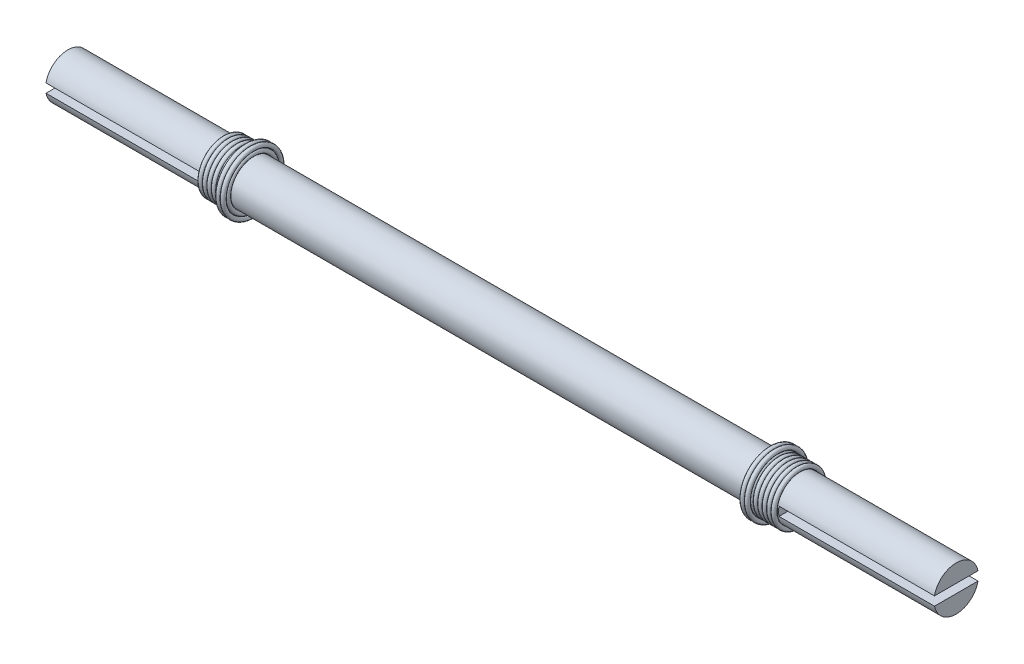
SolidWorks part; units mm, degrees
note: '?' marks a value the reader was unsure of.
ref_plane "前视基准面" through (0, 0, 0) normal (0, 0, 1) x (1, 0, 0)
ref_plane "上视基准面" through (0, 0, 0) normal (0, 1, 0) x (1, 0, 0)
ref_plane "右视基准面" through (0, 0, 0) normal (1, 0, 0) x (0, 0, -1)
sketch "草图1" plane through (0, 0, 0) normal (1, 0, 0) x (0, 0, -1)
  circle A0 centre (0, 0) radius 5
  dimension "D1" = 10
extrude "凸台-拉伸1" add sketch "草图1" along normal blind 100
ref_plane "基准面4" through (100, 0, 0) normal (1, 0, 0) x (0, 0, -1)
sketch "草图2" plane through (100, 0, 0) normal (1, 0, 0) x (0, 0, -1)
  line L2 (0, 1) -> (7.2251, 1)
  line L3 (7.2251, 1) -> (7.2251, -1)
  line L4 (7.2251, -1) -> (-6.4557, -1)
  line L5 (-6.4557, -1) -> (-6.4557, 1)
  line L6 (-6.4557, 1) -> (0, 1)
extrude "切除-拉伸1" cut sketch "草图2" against normal blind 35
ref_plane "基准面5" through (58.5, 0, 0) normal (1, 0, 0) x (0, 0, -1)
ref_axis "基准轴1" through (100, 0, 0) along (-1, 0, 0)?
sketch "草图3" plane through (58.5, 0, 0) normal (1, 0, 0) x (0, 0, -1)
  circle A0 centre (0, 0) radius 5.5
  dimension "D1" = 11
sketch "草图4" plane through (0, 0, 0) normal (0, 0, 1) x (1, 0, 0)
  circle A0 centre (58.5, 5.5) radius 0.5
  dimension "D1" = 1
surface "曲面-扫描1"
pattern_linear "阵列(线性)1" count 7 spacing 1 along (1, 0, 0) of bodies 109
sketch "草图5" plane through (58.5, 0, 0) normal (1, 0, 0) x (0, 0, -1)
  circle A0 centre (0, 0) radius 6.5
  dimension "D1" = 13
sketch "草图6" plane through (0, 0, 0) normal (0, 0, 1) x (1, 0, 0)
  circle A0 centre (58.5, 6.5) radius 0.5
surface "曲面-扫描2"
pattern_linear "阵列(线性)2" count 2 spacing 1 along (1, 0, 0) of bodies 116
mirror "镜向1" about plane through (0, 0, 0) normal (1, 0, 0) of bodies 115 114 113 112 111 110 116 117 109 107
